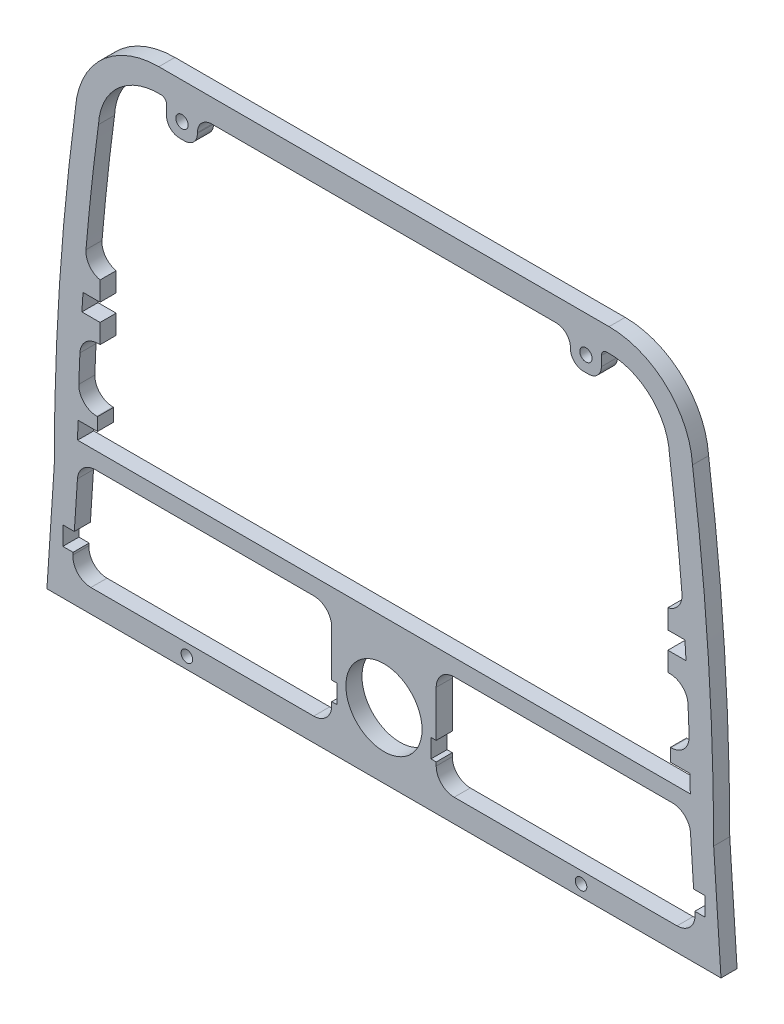
SolidWorks part; units mm, degrees
material "Delrin 2700 NC010, Low Viscosity Acetal Copolymer (SS)"
ref_plane "Front Plane" through (0, 0, 0) normal (0, 0, 1) x (1, 0, 0)
ref_plane "Top Plane" through (0, 0, 0) normal (0, 1, 0) x (1, 0, 0)
ref_plane "Right Plane" through (0, 0, 0) normal (1, 0, 0) x (0, 0, -1)
sketch "Sketch1" plane through (0, 0, 0) normal (0, 0, 1) x (1, 0, 0)
  line L0 (32.5509, -11.3075) -> (33.274, -22.225)
  line L1 (22.225, 27.94) -> (-22.225, 27.94)
  line L2 (-33.274, -22.225) -> (-30.462, 20.2306) construction
  line L3 (-32.5509, -11.3075) -> (-32.5509, 14.6458) construction
  line L4 (-32.5509, -11.3075) -> (-33.274, -22.225)
  line L5 (16.9823, 25.654) -> (-16.9823, 25.654)
  line L6 (30.1502, -9.652) -> (30.5687, -15.9702)
  line L7 (-30.8316, -19.939) -> (-19.9655, -19.939)
  line L8 (-33.274, -22.225) -> (33.274, -22.225)
  line L9 (-30.1502, -9.652) -> (-30.5687, -15.9702)
  line L10 (-18.415, 24.2213) -> (-18.415, 24.13)
  line L11 (-19.685, 22.86) -> (-20.193, 22.86)
  line L12 (-21.463, 24.13) -> (-21.463, 25.0906)
  line L13 (18.415, 24.2213) -> (18.415, 24.13)
  line L14 (19.685, 22.86) -> (20.193, 22.86)
  line L15 (21.463, 24.13) -> (21.463, 25.0906)
  line L16 (30.181, -5.0038) -> (28.276, -5.0038)
  line L17 (28.276, -5.0038) -> (28.276, -6.2738)
  line L18 (0, 18.415) -> (0, -18.415) construction
  line L19 (-29.7095, 4.9022) -> (-28.0257, 4.9022)
  line L20 (28.276, -6.2738) -> (30.2114, -6.2738)
  line L21 (-18.9495, -19.939) -> (-5.1562, -19.939)
  line L22 (22.225, 25.654) -> (-22.225, 25.654) construction
  line L23 (-30.2649, -11.383) -> (-30.8316, -19.939) construction
  line L24 (29.9307, 1.27) -> (28.0257, 1.27)
  line L25 (28.0257, 1.27) -> (28.0257, 3.175)
  line L26 (28.0257, 3.175) -> (29.8217, 3.175)
  line L27 (29.7095, 4.9022) -> (28.0257, 4.9022)
  line L28 (5.1562, -19.939) -> (18.9495, -19.939)
  line L29 (-30.8316, -19.939) -> (30.8316, -19.939) construction
  line L30 (19.9655, -19.939) -> (30.8316, -19.939)
  line L31 (30.2649, -11.383) -> (30.8316, -19.939) construction
  line L32 (28.0257, 4.9022) -> (28.0257, 6.8072)
  line L33 (28.0257, 6.8072) -> (29.5711, 6.8072)
  line L34 (-30.2418, -8.001) -> (30.2418, -8.001)
  line L35 (-5.1562, -9.652) -> (-5.1562, -15.9702)
  line L36 (-30.1502, -9.652) -> (-5.1562, -9.652)
  line L37 (5.1562, -9.652) -> (30.1502, -9.652)
  line L38 (-30.2418, -9.652) -> (30.2418, -9.652) construction
  line L39 (5.1562, -9.652) -> (5.1562, -15.9702)
  line L40 (18.415, 24.384) -> (19.939, 24.384) construction
  line L41 (19.939, 24.384) -> (21.463, 24.384) construction
  line L42 (19.939, 24.384) -> (19.939, 22.86) construction
  line L43 (19.939, 22.86) -> (19.939, 23.7744) construction
  line L44 (-28.0257, 4.9022) -> (-28.0257, 6.8072)
  line L45 (-28.0257, 6.8072) -> (-29.5711, 6.8072)
  line L46 (-28.276, -6.2738) -> (-30.2114, -6.2738)
  line L47 (-28.276, -5.0038) -> (-28.276, -6.2738)
  line L48 (-30.181, -5.0038) -> (-28.276, -5.0038)
  line L49 (-28.0257, 3.175) -> (-29.8217, 3.175)
  line L50 (-28.0257, 1.27) -> (-28.0257, 3.175)
  line L51 (-29.9307, 1.27) -> (-28.0257, 1.27)
  line L52 (-5.1562, -17.8117) -> (-5.1562, -19.939)
  line L53 (-30.6907, -17.8117) -> (-30.8316, -19.939)
  line L54 (-30.5687, -15.9702) -> (-31.7041, -15.9702)
  line L55 (-31.7041, -15.9702) -> (-31.7041, -17.8117)
  line L57 (-26.9289, -16.0973) -> (-30.1101, -16.0973) construction
  line L58 (-31.3801, -17.6848) -> (-31.3801, -16.0973) construction
  line L59 (-31.3801, -17.6848) -> (-31.3801, -16.0973) construction
  line L60 (-5.1562, -17.6847) -> (-4.7671, -17.6848) construction
  line L61 (-31.7041, -17.8117) -> (-30.6907, -17.8117)
  line L62 (-4.7671, -16.0973) -> (-5.1562, -16.0972) construction
  line L63 (-4.7671, -17.6848) -> (-4.7671, -16.0973) construction
  line L64 (-31.3801, -16.0973) -> (-32.3961, -16.0973) construction
  line L65 (-31.3801, -16.0973) -> (-32.3961, -16.0973) construction
  line L67 (-26.9289, -16.0973) -> (-30.1101, -16.0973)
  line L68 (-31.3801, -17.6848) -> (-32.3961, -17.6848) construction
  line L72 (-5.1562, -17.8117) -> (-4.6401, -17.8117)
  line L74 (-4.6401, -17.8117) -> (-4.6401, -15.9702)
  line L75 (-4.6401, -15.9702) -> (-5.1562, -15.9702)
  line L76 (30.3302, -15.9702) -> (30.5687, -15.9702)
  line L77 (31.7041, -17.8117) -> (30.6907, -17.8117)
  line L78 (30.3302, -15.9702) -> (31.7041, -15.9702)
  line L79 (31.7041, -15.9702) -> (31.7041, -17.8117)
  line L80 (5.1562, -17.8117) -> (4.6401, -17.8117)
  line L81 (4.6401, -17.8117) -> (4.6401, -15.9702)
  line L82 (4.6401, -15.9702) -> (5.1562, -15.9702)
  line L83 (5.1562, -17.8117) -> (5.1562, -19.939)
  line L84 (30.6907, -17.8117) -> (30.8316, -19.939)
  line L85 (-19.4575, -19.939) -> (-19.4575, -22.225) construction
  line L86 (-18.9495, -19.939) -> (-19.9655, -19.939)
  line L87 (19.9655, -19.939) -> (18.9495, -19.939)
  arc A0 (22.225, 27.94) -> (30.462, 20.2306) centre (22.225, 19.685) cw
  arc A1 (-22.225, 27.94) -> (-30.462, 20.2306) centre (-22.225, 19.685) ccw
  arc A2 (32.5509, -11.3075) -> (30.462, 20.2306) centre (-206.5707, -11.3075) ccw
  circle A3 centre (0, -15.748) radius 3.7592
  circle A4 centre (19.4575, -21.082) radius 0.5715
  arc A5 (-32.5509, -11.3075) -> (-30.462, 20.2306) centre (206.5707, -11.3075) cw
  arc A6 (-30.2649, -11.383) -> (-30.2649, -11.3075) centre (206.5707, -11.3075) cw
  arc A7 (-20.193, 22.86) -> (-21.463, 24.13) centre (-20.193, 24.13) cw
  arc A8 (30.181, -5.0038) -> (29.9307, 1.27) centre (-206.5707, -11.3075) ccw
  circle A9 centre (-19.939, 24.384) radius 0.6096
  circle A10 centre (19.939, 24.384) radius 0.6096
  circle A12 centre (-19.4575, -21.082) radius 0.5715
  arc A14 (-18.415, 24.13) -> (-19.685, 22.86) centre (-19.685, 24.13) cw
  arc A15 (-16.9823, 25.654) -> (-18.415, 24.2213) centre (-16.9823, 24.2213) ccw
  arc A16 (-21.463, 25.0906) -> (-22.0016, 25.6498) centre (-22.0226, 25.0906) ccw
  arc A17 (16.9823, 25.654) -> (18.415, 24.2213) centre (16.9823, 24.2213) cw
  arc A18 (-22.0016, 25.6498) -> (-28.1851, 20.0099) centre (-22.225, 19.685) ccw
  arc A19 (22.0016, 25.6498) -> (28.1851, 20.0099) centre (22.225, 19.685) cw
  arc A20 (30.2649, -11.383) -> (30.2649, -11.3075) centre (-206.5707, -11.3075) ccw
  arc A21 (18.415, 24.13) -> (19.685, 22.86) centre (19.685, 24.13) ccw
  arc A22 (20.193, 22.86) -> (21.463, 24.13) centre (20.193, 24.13) ccw
  arc A23 (21.463, 25.0906) -> (22.0016, 25.6498) centre (22.0226, 25.0906) cw
  arc A24 (29.5711, 6.8072) -> (28.1851, 20.0099) centre (-206.5707, -11.3075) ccw
  arc A25 (29.8217, 3.175) -> (29.7095, 4.9022) centre (-206.5707, -11.3075) ccw
  arc A26 (-29.5711, 6.8072) -> (-28.1851, 20.0099) centre (206.5707, -11.3075) cw
  arc A27 (22.225, 25.654) -> (28.1851, 20.0099) centre (22.225, 19.685) cw construction
  arc A28 (-22.225, 25.654) -> (-28.1851, 20.0099) centre (-22.225, 19.685) ccw construction
  arc A29 (30.2418, -8.001) -> (30.2114, -6.2738) centre (-206.5707, -11.3075) ccw
  arc A30 (-30.2649, -11.383) -> (-28.1851, 20.0099) centre (206.5707, -11.3075) cw construction
  arc A31 (-29.8217, 3.175) -> (-29.7095, 4.9022) centre (206.5707, -11.3075) cw
  arc A32 (30.2649, -11.383) -> (28.1851, 20.0099) centre (-206.5707, -11.3075) ccw construction
  arc A33 (-30.2418, -8.001) -> (-30.2114, -6.2738) centre (206.5707, -11.3075) cw
  arc A34 (-30.181, -5.0038) -> (-29.9307, 1.27) centre (206.5707, -11.3075) cw
  point P0 (0, 0)
  point P1 (0, 27.94)
  point P26 (0, -22.225)
  point P104 (-3.7592, -15.748)
  point P127 (-30.4335, -17.8117)
  dimension "D4" = 2.286
  dimension "D6" = 8.255
  dimension "D7" = 19.4575
  dimension "D8" = 50.165
  dimension "D9" = 6.477
  dimension "D5" = 1.2192
  dimension "D17" = 1.143
  dimension "D3" = 7.5184
  dimension "D18" = 0.127
  dimension "D19" = 1.27
  dimension "D20" = 1.27
  dimension "D31" = 0.5596
  dimension "D32" = 1.4327
  dimension "D2" = 44.45
  dimension "D10" = 0.127
  dimension "D11" = 1.27
  dimension "D12" = 66.548
  dimension "D13" = 19.939
  dimension "D14" = 11.938
  dimension "D15" = 5.1562
  dimension "D16" = 15.748
  dimension "D21" = 1.27
  dimension "D22" = 1.905
  dimension "D23" = 1.7272
  dimension "D24" = 2.4007
  dimension "D25" = 1.905
  dimension "D26" = 1.7272
  dimension "D27" = 11.176
  dimension "D28" = 1.651
  dimension "D30" = 0.508
  dimension "D29" = 1.0134
  dimension "D35" = 0.127
extrude "Boss-Extrude1" add sketch "Sketch1" along normal blind 1.5875 contours A20 | A6 | A6 | A20 | A5 L4 L8 L0 A2 A0 L1 A1 A29 L34 A18 A16 L12 A7 L11 A14 L10 A15 L5 A17 L13 A21 L14 A22 L15 A23 A19 A24 L33 L32 L27 A25 L26 L25 L24 A8 L16 L17 L20 A12 L86 L7 L9 L36 region at (32.0809, -16.8213, 0)
ref_axis "Axis1" through (0, -15.748, 0) along (0, 0, 1)
fillet "Fillet1" radius 1.778 14 edges at (-30.181, -5.0038, 0.7937) (-29.9307, 1.27, 0.7937) (-29.5711, 6.8072, 0.7937) (29.9307, 1.27, 0.7937) (29.5711, 6.8072, 0.7937) (30.181, -5.0038, 0.7937) (-30.1502, -9.652, 0.7937) (-5.1562, -9.652, 0.7937) (5.1562, -9.652, 0.7937) (30.1502, -9.652, 0.7937) (-30.8316, -19.939, 0.7937) (-5.1562, -19.939, 0.7937) (5.1562, -19.939, 0.7937) (30.8316, -19.939, 0.7937)
